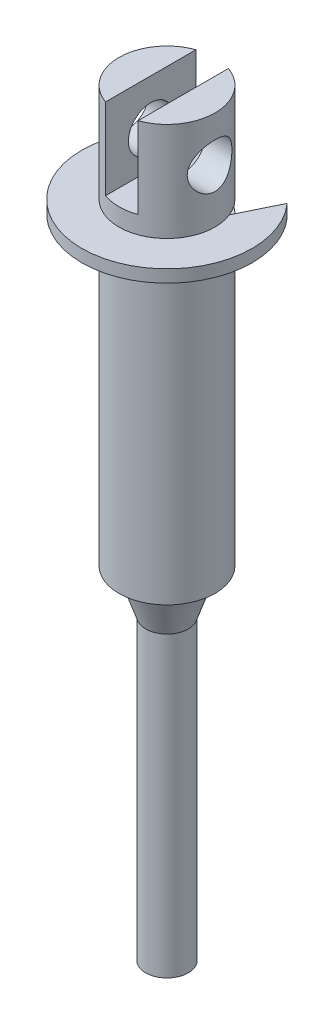
SolidWorks part; units mm, degrees
ref_plane "Front Plane" through (0, 0, 0) normal (0, 0, 1) x (1, 0, 0)
ref_plane "Top Plane" through (0, 0, 0) normal (0, 1, 0) x (1, 0, 0)
ref_plane "Right Plane" through (0, 0, 0) normal (1, 0, 0) x (0, 0, -1)
sketch "Sketch2" plane through (0, 0, 0) normal (1, 0, 0) x (0, 0, -1)
  line L0 (0, 0) -> (2, 0)
  line L1 (2, 0) -> (2, 27.94)
  line L2 (2, 27.94) -> (3.3973, 32.0802)
  line L3 (3.3973, 32.0802) -> (4.5085, 32.0802)
  line L4 (4.5085, 32.0802) -> (4.5085, 60.6806)
  line L5 (4.5085, 60.6806) -> (4.1275, 60.6806)
  line L6 (4.1275, 60.6806) -> (4.1275, 61.849)
  line L7 (4.1275, 61.849) -> (4.5085, 61.849)
  line L8 (4.5085, 61.849) -> (4.5085, 71.12)
  line L9 (4.5085, 71.12) -> (0, 71.12)
  line L10 (0, 71.12) -> (0, 0)
  dimension "D1" = 2
  dimension "D2" = 27.94
  dimension "D3" = 3.3973
  dimension "D4" = 4.5085
  dimension "D5" = 4.1402
  dimension "D6" = 1.1684
  dimension "D7" = 0.381
  dimension "D8" = 9.271
  dimension "D9" = 71.12
revolve "Revolve1" add sketch "Sketch2" angle 360 about L10
sketch "Sketch3" plane through (0, 0, 0) normal (0, 0, 1) x (1, 0, 0)
  line L0 (4.5085, 71.12) -> (-4.5085, 71.12) construction
  line L1 (-1.524, 71.12) -> (1.524, 71.12)
  line L2 (-1.524, 71.12) -> (-1.524, 63.5)
  line L3 (-1.524, 63.5) -> (1.524, 63.5)
  line L4 (1.524, 71.12) -> (1.524, 63.5)
  line L5 (-4.5085, 71.12) -> (4.5085, 71.12) construction
  point P10 (0, 71.12)
  point P11 (0, 71.12)
  dimension "D1" = 3.048
  dimension "D2" = 7.62
extrude "Cut-Extrude1" cut sketch "Sketch3" against normal through all both and the other way through all
sketch "Sketch4" plane through (1.524, 0, 0) normal (-1, 0, 0) x (0, 0, 1)
  line L0 (4.2431, 71.12) -> (-4.2431, 71.12) construction
  line L1 (0, 71.12) -> (0, 66.8401) construction
  circle A0 centre (0, 66.8401) radius 2.0955
  point P2 (0, 68.9356)
  point P8 (0, 0)
  dimension "D1" = 4.191
  dimension "D2" = 2.1844
extrude "Cut-Extrude2" cut sketch "Sketch4" against normal through all both and the other way through all
sketch "Sketch5" plane through (0, 61.849, 0) normal (0, -1, 0) x (1, 0, 0)
  line L0 (-5.969, -5.3089) -> (-4.191, -1.662)
  line L1 (4.191, -1.662) -> (5.969, -5.3089)
  line L2 (0, 0) -> (0, -6.1091) construction
  arc A0 (5.969, -5.3089) -> (-5.969, -5.3089) centre (0, 0) ccw
  circle A1 centre (0, 0) radius 4.5085 construction
  circle A2 centre (0, 0) radius 4.5085
  point P10 (4.2051, -1.6259)
  point P11 (0, 0)
  point P12 (0, 0)
  point P13 (0, 0)
  circle M1 centre (0, 0) radius 4.5085
  dimension "D1" = 15.9766
  dimension "D2" = 11.938
  dimension "D3" = 8.382
extrude "Boss-Extrude1" add sketch "Sketch5" along normal up to surface (1.1684 mm away) separate body contours L1 A0 L0 M1 region at (0, 61.849, 7.7804) up to face at (0, 60.6806, 4.1275)
